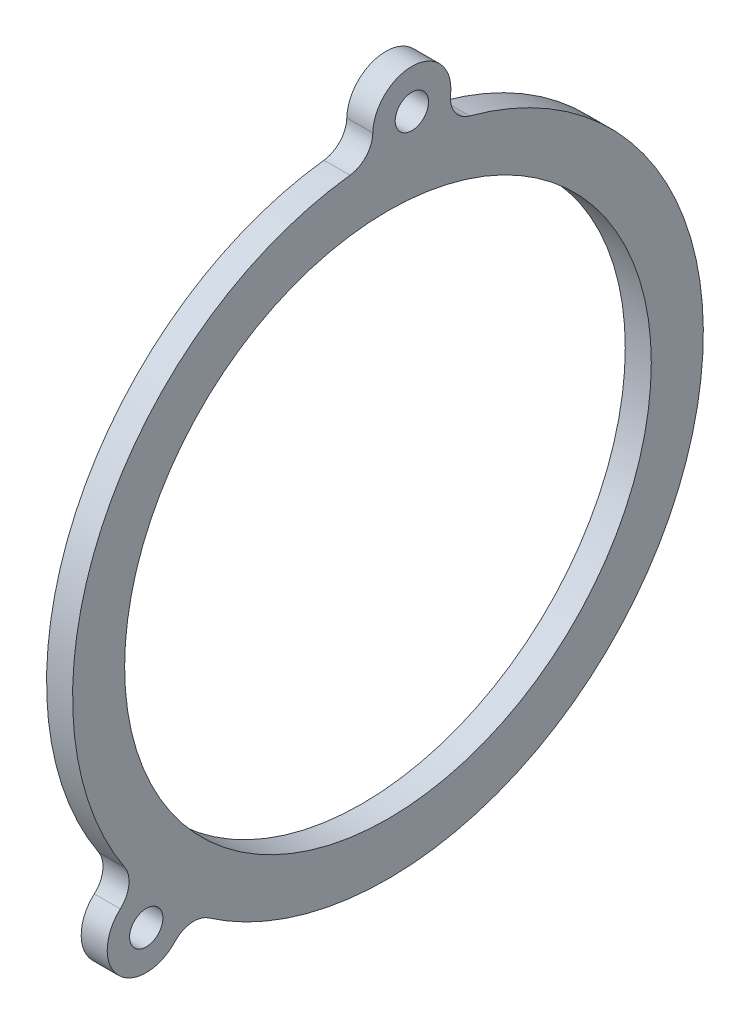
SolidWorks part; units mm, degrees
ref_plane "Front Plane" through (0, 0, 0) normal (0, 0, 1) x (1, 0, 0)
ref_plane "Top Plane" through (0, 0, 0) normal (0, 1, 0) x (1, 0, 0)
ref_plane "Right Plane" through (0, 0, 0) normal (1, 0, 0) x (0, 0, -1)
sketch "Sketch1" plane through (0, 0, 0) normal (1, 0, 0) x (0, 0, -1)
  circle A0 centre (0, 0) radius 32.131
  arc A1 (-1.0056, 38.4679) -> (-29.971, -24.1355) centre (0, 0) ccw
  arc A2 (6.4151, 37.9425) -> (-1.0056, 38.4679) centre (2.9148, 41.172) ccw
  arc A3 (-29.971, -24.1355) -> (-24.7669, -29.4515) centre (-29.4943, -28.8741) ccw
  arc A4 (-24.7669, -29.4515) -> (6.4151, 37.9425) centre (0, 0) ccw
  circle A5 centre (2.9148, 41.172) radius 2.032
  circle A6 centre (-29.4943, -28.8741) radius 2.032
  circle A7 centre (2.9148, 41.172) radius 2.032 construction
  circle A8 centre (-29.4943, -28.8741) radius 2.032 construction
  dimension "D1" = 64.262
  dimension "D2" = 6.35
  dimension "D3" = 4.064
  dimension "D4" = 9.525
extrude "Boss-Extrude1" add sketch "Sketch1" along normal blind 3.175
fillet "Fillet1" radius 3.175 4 edges at (1.5875, -29.4515, 24.7669) (1.5875, -24.1355, 29.971) (1.5875, 37.9425, -6.4151) (1.5875, 38.4679, 1.0056)
